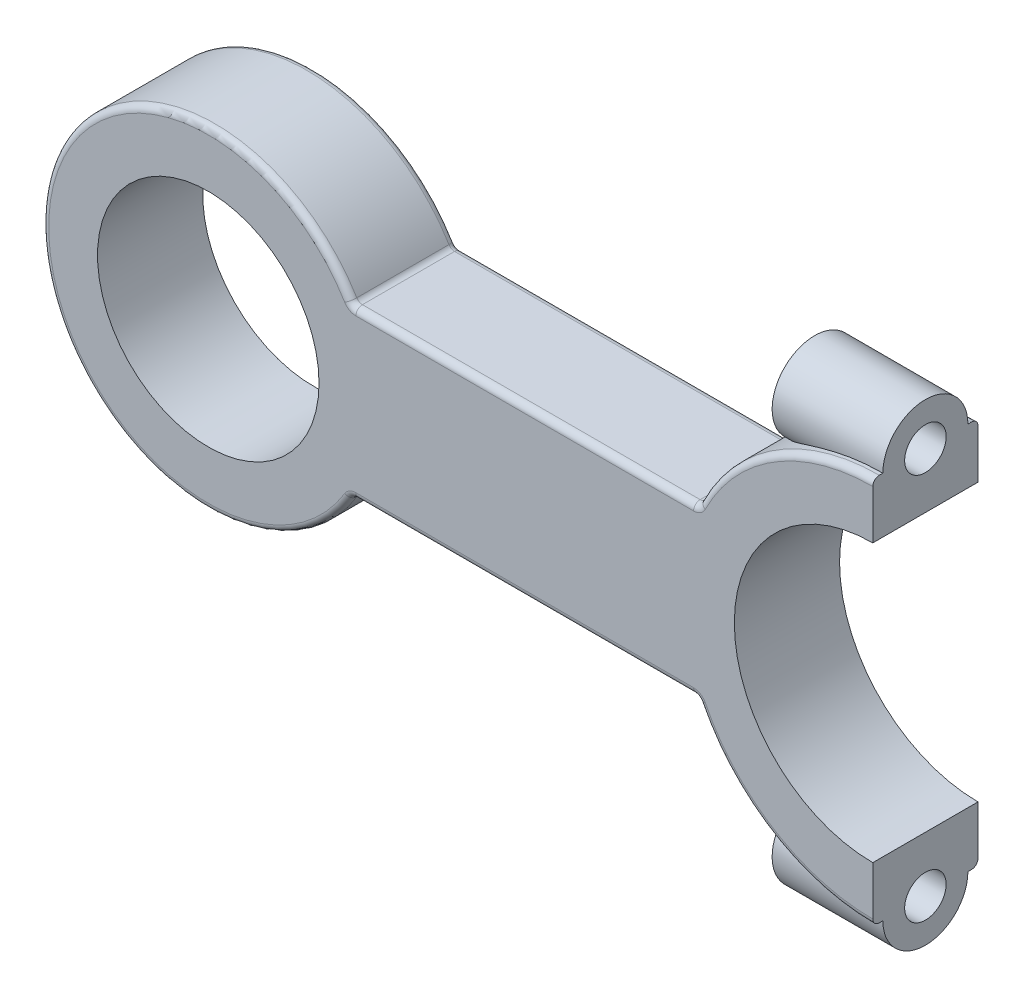
SolidWorks part; units mm, degrees
material "AISI 4340 Steel, normalized"
ref_plane "Front Plane" through (0, 0, 0) normal (0, 0, 1) x (1, 0, 0)
ref_plane "Top Plane" through (0, 0, 0) normal (0, 1, 0) x (1, 0, 0)
ref_plane "Right Plane" through (0, 0, 0) normal (1, 0, 0) x (0, 0, -1)
sketch "Sketch1" plane through (0, 0, 0) normal (0, 0, 1) x (1, 0, 0)
  line L0 (152.4, 44.45) -> (152.4, 31.75)
  line L1 (152.4, -31.75) -> (152.4, -44.45)
  line L2 (32.9956, 19.05) -> (112.2391, 19.05)
  line L3 (32.9956, -19.05) -> (112.2391, -19.05)
  circle A0 centre (0, 0) radius 25.4
  circle A1 centre (0, 0) radius 38.1
  arc A2 (152.4, 31.75) -> (152.4, -31.75) centre (152.4, 0) ccw
  arc A3 (152.4, 44.45) -> (152.4, -44.45) centre (152.4, 0) ccw
  dimension "D1" = 76.2
  dimension "D2" = 50.8
  dimension "D4" = 44.45
  dimension "D5" = 31.75
  dimension "D3" = 152.4
  dimension "D6" = 38.1
extrude "Boss-Extrude2" add sketch "Sketch1" along normal mid plane 24.13 contours A3 L2 A1 L3 | A1 | L0 A2 L1 A3 region at (72.8944, 0, 0)
sketch "Sketch4" plane through (0, 0, 12.065) normal (0, 0, 1) x (1, 0, 0)
  circle A0 centre (0, 0) radius 25.4
extrude "Cut-Extrude2" cut sketch "Sketch4" against normal through all both and the other way through all
sketch "Sketch5" plane through (152.4, 0, 0) normal (1, 0, 0) x (0, 0, -1)
  line L0 (-12.065, 44.45) -> (12.065, 44.45) construction
  circle A0 centre (0, 44.45) radius 9.75
  dimension "D1" = 19.5
extrude "Boss-Extrude4" add sketch "Sketch5" against normal blind 25.4
sketch "Sketch6" plane through (152.4, 0, 0) normal (1, 0, 0) x (0, 0, -1)
  circle A0 centre (0, 44.45) radius 4.76
  dimension "D1" = 9.52
extrude "Cut-Extrude3" cut sketch "Sketch6" against normal blind 25.4 and the other way through all
mirror "Mirror2" about plane through (0, 0, 0) normal (0, 1, 0) of "Boss-Extrude4", "Cut-Extrude3"
fillet "Fillet3" radius 1.5 14 edges at (72.6173, -19.05, -12.065) (72.6173, -19.05, 12.065) (72.6173, 19.05, 12.065) (72.6173, 19.05, -12.065) (-38.1, 0, 12.065) (-38.1, 0, -12.065) (128.6405, -37.5671, 12.065) (128.6405, -37.5671, -12.065) (128.6405, 37.5671, 12.065) (128.6405, 37.5671, -12.065) (32.9956, -19.05, 0) (112.2391, -19.05, 0) (112.2391, 19.05, 0) (32.9956, 19.05, 0)
